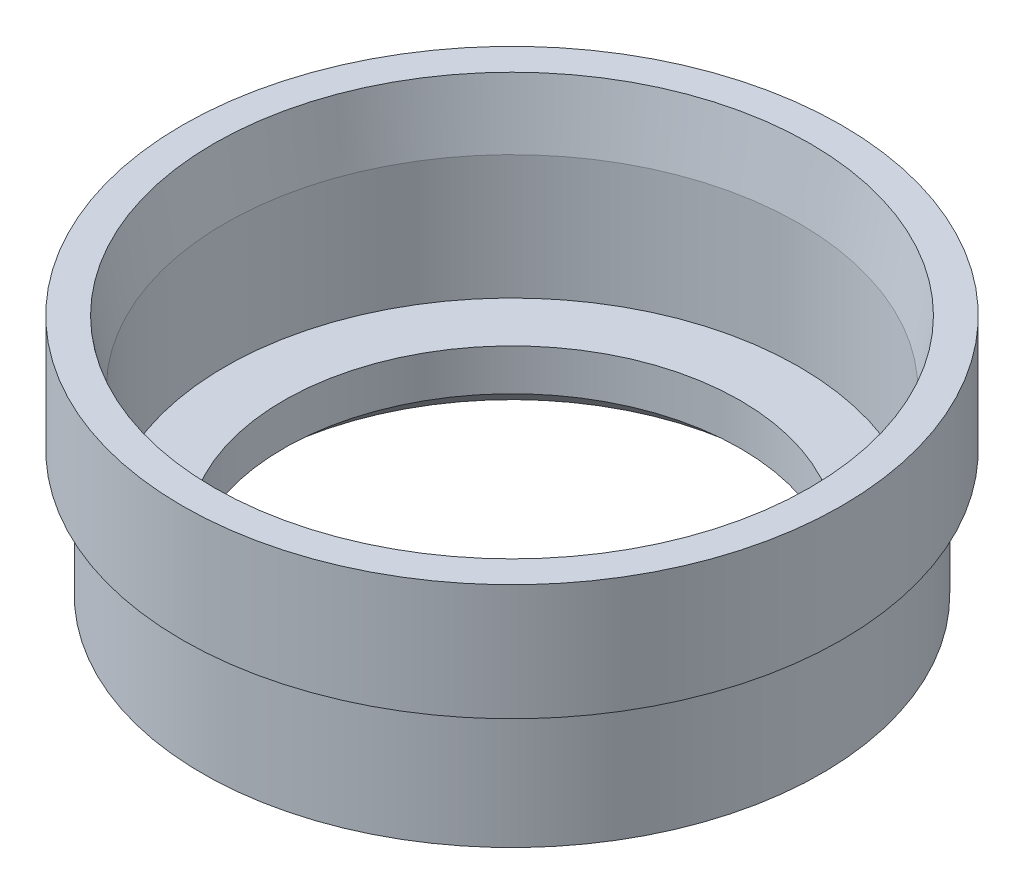
SolidWorks part; units mm, degrees
ref_plane "Front Plane" through (0, 0, 0) normal (0, 0, 1) x (1, 0, 0)
ref_plane "Top Plane" through (0, 0, 0) normal (0, 1, 0) x (1, 0, 0)
ref_plane "Right Plane" through (0, 0, 0) normal (1, 0, 0) x (0, 0, -1)
sketch "Sketch2" plane through (0, 0, 0) normal (0, 0, 1) x (1, 0, 0)
  line L0 (0, 5.2456) -> (0, 8.6395)
  line L1 (0, 8.6395) -> (4.8, 8.6395)
  line L2 (4.8, 8.6395) -> (4.8, 18.8103)
  line L3 (4.8, 18.8103) -> (5.7059, 24.0144)
  line L7 (6.65, 14.5056) -> (6.65, 4.2056)
  line L8 (6.65, 4.2056) -> (3.7962, 4.2056)
  line L9 (3.7962, 4.2056) -> (3.7962, 3.2056)
  line L10 (3.7962, 3.2056) -> (2.2962, 3.2056)
  line L11 (2.2962, 3.2056) -> (0, 5.2456)
  line L13 (-18.7, 7.4362) -> (-18.7, 16.9661)
  line L14 (6.65, 24.0144) -> (5.7059, 24.0144)
  line L15 (6.65, 14.5056) -> (8.3, 14.5056)
  line L16 (8.3, 14.5056) -> (8.3, 24.0144)
  line L17 (6.65, 24.0144) -> (8.3, 24.0144)
  dimension "D1" = 27
  dimension "D4" = 6.65
  dimension "D5" = 1.5
  dimension "D6" = 25.35
  dimension "D7" = 10.3
revolve "Revolve1" add sketch "Sketch2" angle 360 about L13 region at (5.1096, 12.4925, 0)
